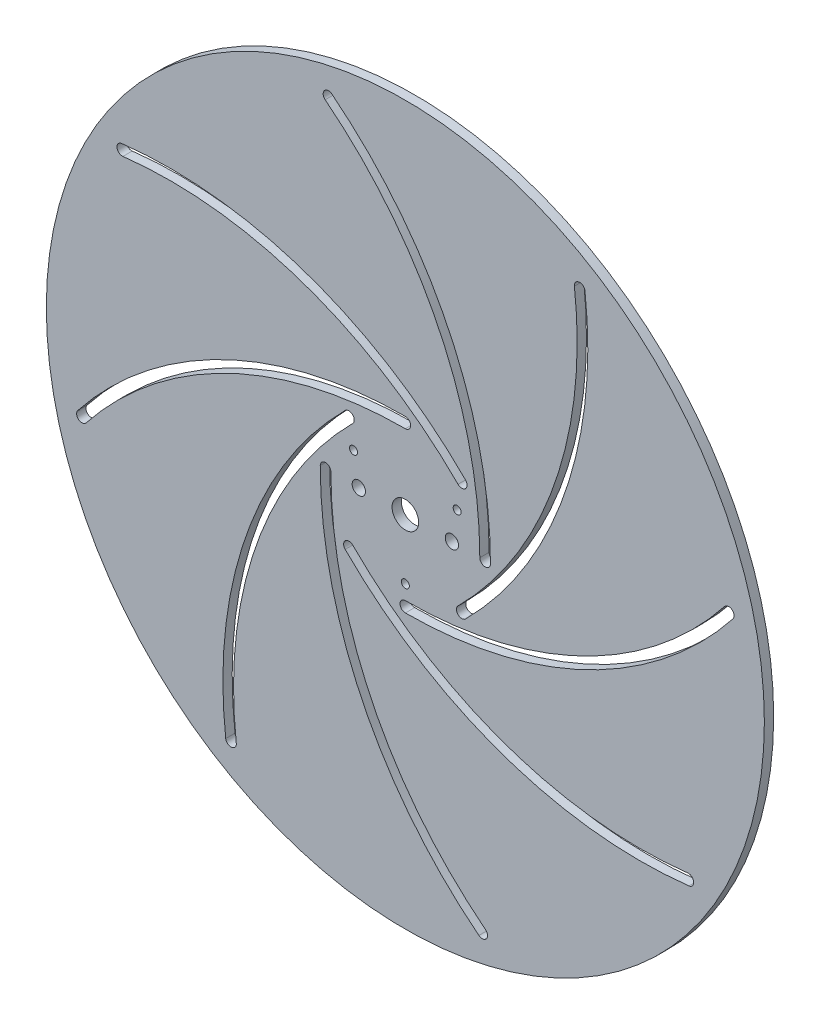
SolidWorks part; units mm, degrees
ref_plane "Front Plane" through (0, 0, 0) normal (0, 0, 1) x (1, 0, 0)
ref_plane "Top Plane" through (0, 0, 0) normal (0, 1, 0) x (1, 0, 0)
ref_plane "Right Plane" through (0, 0, 0) normal (1, 0, 0) x (0, 0, -1)
sketch "Sketch1" plane through (0, 0, 0) normal (0, 0, 1) x (1, 0, 0)
  line L0 (30, 0) -> (-135, 0) construction
  line L1 (0, 30) -> (0, -125) construction
  circle A0 centre (0, 0) radius 135
  circle A2 centre (0, 0) radius 30 construction
  circle A3 centre (0, 0) radius 125 construction
  arc A4 (0, 30) -> (-121.6133, -28.9) centre (0, -125) ccw construction
  arc A5 (0, 32) -> (-123.1825, -27.66) centre (0, -125) ccw
  arc A6 (0, 28) -> (-120.0441, -30.14) centre (0, -125) ccw
  arc A7 (0, 28) -> (0, 32) centre (0, 30) ccw
  arc A8 (-123.1825, -27.66) -> (-120.0441, -30.14) centre (-121.6133, -28.9) ccw
  arc A9 (21.2132, 21.2132) -> (-106.429, 65.5582) centre (-88.3883, -88.3883) ccw construction
  arc A14 (22.6274, 22.6274) -> (-106.6617, 67.5446) centre (-88.3883, -88.3883) ccw
  arc A19 (19.799, 19.799) -> (-106.1962, 63.5718) centre (-88.3883, -88.3883) ccw
  arc A24 (19.799, 19.799) -> (22.6274, 22.6274) centre (21.2132, 21.2132) ccw
  arc A29 (-106.6617, 67.5446) -> (-106.1962, 63.5718) centre (-106.429, 65.5582) ccw
  arc A35 (30, 0) -> (-28.9, 121.6133) centre (-125, 0) ccw construction
  arc A36 (32, 0) -> (-27.66, 123.1825) centre (-125, 0) ccw
  arc A37 (28, 0) -> (-30.14, 120.0441) centre (-125, 0) ccw
  arc A38 (28, 0) -> (32, 0) centre (30, 0) ccw
  arc A39 (-27.66, 123.1825) -> (-30.14, 120.0441) centre (-28.9, 121.6133) ccw
  arc A40 (21.2132, -21.2132) -> (65.5582, 106.429) centre (-88.3883, 88.3883) ccw construction
  arc A41 (22.6274, -22.6274) -> (67.5446, 106.6617) centre (-88.3883, 88.3883) ccw
  arc A42 (19.799, -19.799) -> (63.5718, 106.1962) centre (-88.3883, 88.3883) ccw
  arc A43 (19.799, -19.799) -> (22.6274, -22.6274) centre (21.2132, -21.2132) ccw
  arc A44 (67.5446, 106.6617) -> (63.5718, 106.1962) centre (65.5582, 106.429) ccw
  arc A45 (0, -30) -> (121.6133, 28.9) centre (0, 125) ccw construction
  arc A46 (0, -32) -> (123.1825, 27.66) centre (0, 125) ccw
  arc A47 (0, -28) -> (120.0441, 30.14) centre (0, 125) ccw
  arc A48 (0, -28) -> (0, -32) centre (0, -30) ccw
  arc A49 (123.1825, 27.66) -> (120.0441, 30.14) centre (121.6133, 28.9) ccw
  arc A50 (-21.2132, -21.2132) -> (106.429, -65.5582) centre (88.3883, 88.3883) ccw construction
  arc A51 (-22.6274, -22.6274) -> (106.6617, -67.5446) centre (88.3883, 88.3883) ccw
  arc A52 (-19.799, -19.799) -> (106.1962, -63.5718) centre (88.3883, 88.3883) ccw
  arc A53 (-19.799, -19.799) -> (-22.6274, -22.6274) centre (-21.2132, -21.2132) ccw
  arc A54 (106.6617, -67.5446) -> (106.1962, -63.5718) centre (106.429, -65.5582) ccw
  arc A55 (-30, 0) -> (28.9, -121.6133) centre (125, 0) ccw construction
  arc A56 (-32, 0) -> (27.66, -123.1825) centre (125, 0) ccw
  arc A57 (-28, 0) -> (30.14, -120.0441) centre (125, 0) ccw
  arc A58 (-28, 0) -> (-32, 0) centre (-30, 0) ccw
  arc A59 (27.66, -123.1825) -> (30.14, -120.0441) centre (28.9, -121.6133) ccw
  arc A60 (-21.2132, 21.2132) -> (-65.5582, -106.429) centre (88.3883, -88.3883) ccw construction
  arc A61 (-22.6274, 22.6274) -> (-67.5446, -106.6617) centre (88.3883, -88.3883) ccw
  arc A62 (-19.799, 19.799) -> (-63.5718, -106.1962) centre (88.3883, -88.3883) ccw
  arc A63 (-19.799, 19.799) -> (-22.6274, 22.6274) centre (-21.2132, 21.2132) ccw
  arc A64 (-67.5446, -106.6617) -> (-63.5718, -106.1962) centre (-65.5582, -106.429) ccw
  circle A65 centre (0, 0) radius 5
  circle A66 centre (-17.5, 0) radius 2.5
  arc A67 (-0.5, 4.9749) -> (0.5556, 4.969) centre (0, 0) cw
  circle A73 centre (0, 0) radius 17.5 construction
  circle A80 centre (17.5, 0) radius 2.5
  circle A81 centre (0, 0) radius 22.5 construction
  circle A84 centre (0, -22.5) radius 1.5
  circle A85 centre (-19.4856, 11.25) radius 1.5
  circle A86 centre (19.4856, 11.25) radius 1.5
  point P11 (-67.5629, 14.5)
  point P22 (-37.5212, 58.0273)
  point P30 (14.5, 67.5629)
  point P38 (58.0273, 37.5212)
  point P46 (67.5629, -14.5)
  point P54 (37.5212, -58.0273)
  point P59 (-0.3062, 0.1031)
  point P63 (-14.5, -67.5629)
  point P71 (-58.0273, -37.5212)
  point P76 (0, 0)
  point P78 (0, 0)
  point P89 (0, 0)
  point P93 (0, 0)
  point P101 (0, 0)
  point P102 (0, 0)
  point P104 (0, 0)
  dimension "D2" = 270
  dimension "D3" = 250
  dimension "D4" = 60
  dimension "D5" = 4
  dimension "D6" = 2
  dimension "D8" = 10
  dimension "D11" = 3
  dimension "D12" = 5
  dimension "D14" = 35
  dimension "D9" = 45
  dimension "D10" = 3
  dimension "D7" = 8
extrude "Boss-Extrude1" add sketch "Sketch1" along normal blind 1.75 and the other way blind 1.75 contours A0 A54 A51 A53 A52 A49 A46 A48 A47 A8 A5 A7 A6 | A65 region at (-131.1816, 0, 0)
